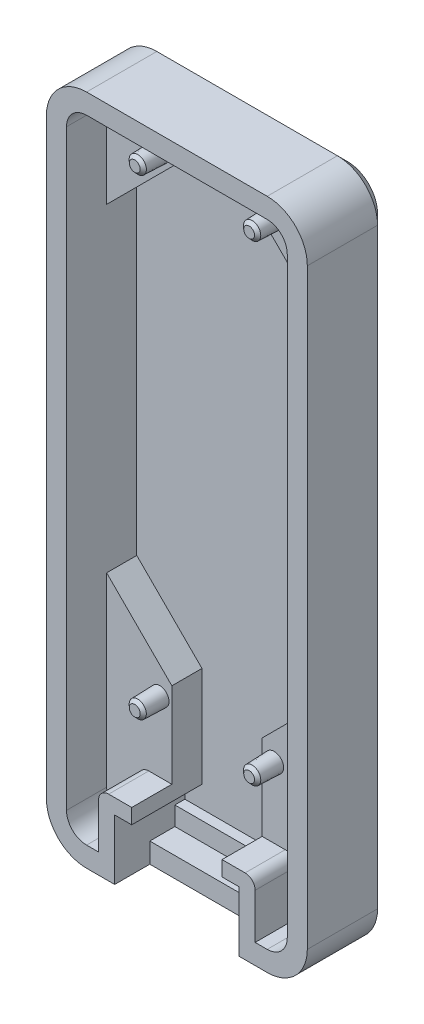
SolidWorks part; units mm, degrees
ref_plane "Front Plane" through (0, 0, 0) normal (0, 0, 1) x (1, 0, 0)
ref_plane "Top Plane" through (0, 0, 0) normal (0, 1, 0) x (1, 0, 0)
ref_plane "Right Plane" through (0, 0, 0) normal (1, 0, 0) x (0, 0, -1)
sketch "Sketch1" plane through (0, 0, 0) normal (0, 0, 1) x (1, 0, 0)
  line L3 (144, 143.2595) -> (140, 143.2595) construction
  line L4 (162, 78.2595) -> (160.8, 78.2595)
  line L5 (140, 139.2595) -> (140, 143.2595) construction
  line L6 (162, 76.2595) -> (166, 76.2595) construction
  line L7 (166, 80.2595) -> (166, 76.2595) construction
  line L8 (162, 76.2595) -> (144, 76.2595)
  line L9 (166, 80.2595) -> (166, 139.2595)
  line L10 (162, 143.2595) -> (144, 143.2595)
  line L11 (140, 80.2595) -> (140, 139.2595)
  line L12 (142, 80.2595) -> (142, 139.2595)
  line L13 (162, 141.2595) -> (144, 141.2595)
  line L14 (164, 80.2595) -> (164, 139.2595)
  line L15 (146.8, 82.2595) -> (146.8, 78.2595)
  line L16 (146.8, 82.2595) -> (148.5, 82.2595)
  line L17 (148.5, 82.2595) -> (148.5, 83.7595)
  line L18 (148.5, 83.7595) -> (146.2, 83.7595)
  line L19 (145.2, 82.7595) -> (145.2, 78.2595)
  line L20 (145.2, 78.2595) -> (144, 78.2595)
  line L21 (162, 78.2595) -> (144, 78.2595) construction
  line L22 (148.5, 82.2595) -> (157.5, 82.2595) construction
  line L23 (153, 82.2595) -> (153, 85.5551) construction
  line L24 (157.5, 82.2595) -> (157.5, 83.7595)
  line L25 (157.5, 83.7595) -> (159.8, 83.7595)
  line L26 (160.8, 82.7595) -> (160.8, 78.2595)
  line L27 (159.2001, 82.2595) -> (159.2001, 78.2595)
  line L28 (159.2001, 82.2595) -> (157.5, 82.2595)
  line L29 (159.2001, 78.2595) -> (146.8, 78.2595)
  arc A0 (144, 76.2595) -> (140, 80.2595) centre (144, 80.2595) cw
  arc A1 (162, 76.2595) -> (166, 80.2595) centre (162, 80.2595) ccw
  arc A2 (166, 139.2595) -> (162, 143.2595) centre (162, 139.2595) ccw
  arc A3 (144, 143.2595) -> (140, 139.2595) centre (144, 139.2595) ccw
  arc A4 (144, 78.2595) -> (142, 80.2595) centre (144, 80.2595) cw
  arc A5 (144, 141.2595) -> (142, 139.2595) centre (144, 139.2595) ccw
  arc A6 (164, 139.2595) -> (162, 141.2595) centre (162, 139.2595) ccw
  arc A7 (162, 78.2595) -> (164, 80.2595) centre (162, 80.2595) ccw
  arc A8 (145.2, 82.7595) -> (146.2, 83.7595) centre (146.2, 82.7595) cw
  arc A9 (160.8, 82.7595) -> (159.8, 83.7595) centre (159.8, 82.7595) ccw
  point P2 (0, 0)
  point P3 (0, 0)
  point P7 (0, 0)
  point P62 (0, 0)
  point P63 (0, 0)
  point P64 (0, 0)
  point P65 (0, 0)
  point P66 (0, 0)
  point P67 (0, 0)
  point P68 (0, 0)
  dimension "D1" = 4
  dimension "D2" = 2
extrude "Boss-Extrude1" add sketch "Sketch1" along normal blind 8
sketch "Sketch2" plane through (0, 0, 0) normal (0, 0, -1) x (-1, 0, 0)
  line L4 (-140, 80.2595) -> (-140, 139.2595)
  line L5 (-144, 143.2595) -> (-162, 143.2595)
  line L6 (-166, 139.2595) -> (-166, 80.2595)
  line L7 (-162, 76.2595) -> (-144, 76.2595)
  line L8 (-140, 80.2595) -> (-140, 139.2595)
  line L9 (-144, 143.2595) -> (-162, 143.2595)
  line L10 (-166, 139.2595) -> (-166, 80.2595)
  line L11 (-162, 76.2595) -> (-144, 76.2595)
  arc A4 (-144, 76.2595) -> (-140, 80.2595) centre (-144, 80.2595) ccw
  arc A5 (-140, 139.2595) -> (-144, 143.2595) centre (-144, 139.2595) ccw
  arc A6 (-162, 143.2595) -> (-166, 139.2595) centre (-162, 139.2595) ccw
  arc A7 (-166, 80.2595) -> (-162, 76.2595) centre (-162, 80.2595) ccw
  arc A8 (-144, 76.2595) -> (-140, 80.2595) centre (-144, 80.2595) ccw
  arc A9 (-140, 139.2595) -> (-144, 143.2595) centre (-144, 139.2595) ccw
  arc A10 (-162, 143.2595) -> (-166, 139.2595) centre (-162, 139.2595) ccw
  arc A11 (-166, 80.2595) -> (-162, 76.2595) centre (-162, 80.2595) ccw
  dimension "D1" = 0
extrude "Boss-Extrude2" add sketch "Sketch2" against normal blind 1
sketch "Sketch3" plane through (0, 0, 1) normal (0, 0, 1) x (1, 0, 0)
  line L0 (142, 130.5618) -> (151.3452, 139.9069)
  line L1 (151.3452, 139.9069) -> (154.6549, 139.9069)
  line L2 (154.6549, 139.9069) -> (164, 130.5617)
  line L3 (142, 98.7595) -> (148.5, 92.2595)
  line L4 (164, 80.2595) -> (164, 139.2595)
  line L5 (162, 141.2595) -> (144, 141.2595)
  line L6 (142, 139.2595) -> (142, 80.2595)
  line L7 (160.8, 78.2595) -> (162, 78.2595)
  line L8 (164, 80.2595) -> (164, 98.7595)
  line L9 (162, 141.2595) -> (144, 141.2595)
  line L10 (142, 139.2595) -> (142, 130.5618)
  line L11 (160.8, 78.2595) -> (162, 78.2595)
  line L12 (148.5, 92.2595) -> (148.5, 83.7595)
  line L18 (157.5, 83.7595) -> (157.5, 92.2595)
  line L19 (157.5, 92.2595) -> (164, 98.7595)
  line L20 (142, 98.7595) -> (142, 80.2595)
  line L21 (164, 130.5617) -> (164, 139.2595)
  line L22 (145.2, 78.2595) -> (145.2, 82.7595)
  line L23 (146.2, 83.7595) -> (148.5, 83.7595)
  line L24 (160.8, 78.2595) -> (160.8, 82.7595)
  line L25 (159.8, 83.7595) -> (157.5, 83.7595)
  line L26 (159.2001, 82.2595) -> (159.2001, 78.2595) construction
  line L27 (146.8, 78.2595) -> (159.2001, 78.2595)
  line L28 (146.8, 78.2595) -> (146.8, 80.1217)
  line L29 (146.8, 80.1217) -> (159.2001, 80.1217)
  line L30 (159.2001, 78.2595) -> (159.2001, 80.1217)
  line L38 (144, 78.2595) -> (145.2, 78.2595)
  line L39 (144, 78.2595) -> (145.2, 78.2595)
  line L40 (145.2, 78.2595) -> (145.2, 82.7595)
  line L42 (146.2, 83.7595) -> (148.5, 83.7595)
  line L44 (148.5, 83.7595) -> (148.5, 82.2595)
  line L46 (148.5, 82.2595) -> (146.8, 82.2595)
  line L48 (146.8, 82.2595) -> (146.8, 78.2595)
  line L50 (146.8, 78.2595) -> (159.2001, 78.2595)
  line L52 (159.2001, 78.2595) -> (159.2001, 82.2595)
  line L54 (159.2001, 82.2595) -> (157.5, 82.2595)
  line L56 (157.5, 82.2595) -> (157.5, 83.7595)
  line L58 (157.5, 83.7595) -> (159.8, 83.7595)
  line L60 (160.8, 82.7595) -> (160.8, 78.2595)
  arc A0 (145.2, 82.7595) -> (146.2, 83.7595) centre (146.2, 82.7595) cw
  arc A4 (162, 78.2595) -> (164, 80.2595) centre (162, 80.2595) ccw
  arc A5 (164, 139.2595) -> (162, 141.2595) centre (162, 139.2595) ccw
  arc A6 (144, 141.2595) -> (142, 139.2595) centre (144, 139.2595) ccw
  arc A7 (142, 80.2595) -> (144, 78.2595) centre (144, 80.2595) ccw
  arc A8 (162, 78.2595) -> (164, 80.2595) centre (162, 80.2595) ccw
  arc A9 (164, 139.2595) -> (162, 141.2595) centre (162, 139.2595) ccw
  arc A10 (144, 141.2595) -> (142, 139.2595) centre (144, 139.2595) ccw
  arc A11 (142, 80.2595) -> (144, 78.2595) centre (144, 80.2595) ccw
  arc A14 (146.2, 83.7595) -> (145.2, 82.7595) centre (146.2, 82.7595) ccw
  arc A16 (160.8, 82.7595) -> (159.8, 83.7595) centre (159.8, 82.7595) ccw
  arc A17 (160.8, 82.7595) -> (159.8, 83.7595) centre (159.8, 82.7595) ccw
  point P31 (0, 0)
  point P32 (0, 0)
  point P33 (0, 0)
  point P34 (0, 0)
  dimension "D1" = 0
extrude "Boss-Extrude3" add sketch "Sketch3" along normal blind 1
sketch "Sketch5" plane through (0, 0, 2) normal (0, 0, 1) x (1, 0, 0)
  circle A0 centre (158.7, 137.7595) radius 1.0048
  circle A1 centre (147.3, 137.7595) radius 1.0048
  circle A2 centre (147.3, 90.7595) radius 1.0048
  circle A3 centre (158.7, 90.7595) radius 1.0048
ref_plane "Plane1" through (0, 0, 6.5) normal (0, 0, 1) x (1, 0, 0)
sketch "Sketch6" plane through (0, 0, 6.5) normal (0, 0, 1) x (1, 0, 0)
  circle A0 centre (147.3, 137.7595) radius 1.0048 construction
  circle A1 centre (158.7, 137.7595) radius 1.0048 construction
  circle A2 centre (147.3, 90.7595) radius 1.0048 construction
  circle A3 centre (158.7, 90.7595) radius 1.0048 construction
  circle A4 centre (147.3, 137.7595) radius 1.0048 construction
  circle A5 centre (158.7, 137.7595) radius 1.0048 construction
  circle A6 centre (147.3, 90.7595) radius 1.0048 construction
  circle A7 centre (158.7, 90.7595) radius 1.0048 construction
  circle A8 centre (147.3, 137.7595) radius 0.85
  circle A9 centre (158.7, 137.7595) radius 0.85
  circle A10 centre (158.7, 90.7595) radius 0.85
  circle A11 centre (147.3, 90.7595) radius 0.85
loft "Loft2" add section "Sketch6" section "Sketch5" start constraint default connector at (159.2756, 90.134, 6.5) connector at (159.4056, 90.0441, 2)
loft "Loft3" add section "Sketch5<3>" section "Sketch6<3>" connector at (147.4441, 89.7651, 2) connector at (147.7636, 90.047, 6.5)
sketch "Sketch5<3>" plane through (0, 0, 2) normal (0, 0, 1) x (1, 0, 0) same geometry as "Sketch5"
sketch "Sketch6<3>" plane through (0, 0, 6.5) normal (0, 0, 1) x (1, 0, 0) same geometry as "Sketch6"
loft "Loft4" add section "Sketch5<4>" section "Sketch6<4>" connector at (158.8197, 136.7618, 2) connector at (158.8332, 136.92, 6.5)
sketch "Sketch5<4>" plane through (0, 0, 2) normal (0, 0, 1) x (1, 0, 0) same geometry as "Sketch5"
sketch "Sketch6<4>" plane through (0, 0, 6.5) normal (0, 0, 1) x (1, 0, 0) same geometry as "Sketch6"
loft "Loft5" add section "Sketch6<6>" section "Sketch5<6>" connector at (147.5382, 136.9435, 6.5) connector at (147.5694, 136.7915, 2)
sketch "Sketch6<6>" plane through (0, 0, 6.5) normal (0, 0, 1) x (1, 0, 0) same geometry as "Sketch6"
sketch "Sketch5<6>" plane through (0, 0, 2) normal (0, 0, 1) x (1, 0, 0) same geometry as "Sketch5"
chamfer "Chamfer1" distance 0.3 angle 45 4 edges at (148.15, 90.7595, 6.5) (159.55, 90.7595, 6.5) (159.55, 137.7595, 6.5) (148.15, 137.7595, 6.5)
chamfer "Chamfer2" distance 1 angle 45 8 edges at (140, 109.7595, 0) (141.1716, 77.431, 0) (141.1716, 142.0879, 0) (153, 76.2595, 0) (153, 143.2595, 0) (164.8285, 77.431, 0) (164.8285, 142.0879, 0) (166, 109.7595, 0)
sketch "Sketch7" plane through (0, 76.2595, 0) normal (0, -1, 0) x (1, 0, 0)
  line L0 (146.8, 8) -> (146.8, 4.5)
  line L3 (146.8, 8) -> (159.2001, 8)
  line L5 (146.8, 4.5) -> (159.2001, 4.5)
  line L6 (159.2001, 4.5) -> (159.2001, 8)
extrude "Cut-Extrude1" cut sketch "Sketch7" against normal blind 3
sketch "Sketch8" plane through (0, 0, 2) normal (0, 0, 1) x (1, 0, 0)
  line L6 (162, 141.2595) -> (144, 141.2595)
  line L7 (142, 139.2595) -> (142, 130.5618)
  line L8 (142, 130.5618) -> (151.3452, 139.9069)
  line L9 (151.3452, 139.9069) -> (154.6549, 139.9069)
  line L10 (154.6549, 139.9069) -> (164, 130.5617)
  line L11 (164, 130.5617) -> (164, 139.2595)
  line L12 (162, 141.2595) -> (144, 141.2595)
  line L13 (142, 139.2595) -> (142, 130.5618)
  line L14 (142, 130.5618) -> (151.3452, 139.9069)
  line L15 (151.3452, 139.9069) -> (154.6549, 139.9069)
  line L16 (154.6549, 139.9069) -> (164, 130.5617)
  line L17 (164, 130.5617) -> (164, 139.2595)
  line L18 (164, 80.2595) -> (164, 98.7595)
  line L19 (164, 98.7595) -> (157.5, 92.2595)
  line L20 (157.5, 92.2595) -> (157.5, 83.7595)
  line L21 (157.5, 83.7595) -> (159.8, 83.7595)
  line L22 (160.8, 82.7595) -> (160.8, 78.2595)
  line L23 (160.8, 78.2595) -> (162, 78.2595)
  line L24 (164, 80.2595) -> (164, 98.7595)
  line L25 (164, 98.7595) -> (157.5, 92.2595)
  line L26 (157.5, 92.2595) -> (157.5, 83.7595)
  line L27 (157.5, 83.7595) -> (159.8, 83.7595)
  line L28 (160.8, 82.7595) -> (160.8, 78.2595)
  line L29 (160.8, 78.2595) -> (162, 78.2595)
  line L30 (146.2, 83.7595) -> (148.5, 83.7595)
  line L31 (148.5, 83.7595) -> (148.5, 92.2595)
  line L32 (148.5, 92.2595) -> (142, 98.7595)
  line L33 (142, 98.7595) -> (142, 80.2595)
  line L34 (144, 78.2595) -> (145.2, 78.2595)
  line L35 (145.2, 78.2595) -> (145.2, 82.7595)
  line L36 (146.2, 83.7595) -> (148.5, 83.7595)
  line L37 (148.5, 83.7595) -> (148.5, 92.2595)
  line L38 (148.5, 92.2595) -> (142, 98.7595)
  line L39 (142, 98.7595) -> (142, 80.2595)
  line L40 (144, 78.2595) -> (145.2, 78.2595)
  line L41 (145.2, 78.2595) -> (145.2, 82.7595)
  arc A2 (164, 139.2595) -> (162, 141.2595) centre (162, 139.2595) ccw
  arc A3 (144, 141.2595) -> (142, 139.2595) centre (144, 139.2595) ccw
  arc A4 (164, 139.2595) -> (162, 141.2595) centre (162, 139.2595) ccw
  arc A5 (144, 141.2595) -> (142, 139.2595) centre (144, 139.2595) ccw
  arc A6 (162, 78.2595) -> (164, 80.2595) centre (162, 80.2595) ccw
  arc A7 (160.8, 82.7595) -> (159.8, 83.7595) centre (159.8, 82.7595) ccw
  arc A8 (162, 78.2595) -> (164, 80.2595) centre (162, 80.2595) ccw
  arc A9 (160.8, 82.7595) -> (159.8, 83.7595) centre (159.8, 82.7595) ccw
  arc A10 (146.2, 83.7595) -> (145.2, 82.7595) centre (146.2, 82.7595) ccw
  arc A11 (142, 80.2595) -> (144, 78.2595) centre (144, 80.2595) ccw
  arc A12 (146.2, 83.7595) -> (145.2, 82.7595) centre (146.2, 82.7595) ccw
  arc A13 (142, 80.2595) -> (144, 78.2595) centre (144, 80.2595) ccw
  dimension "D1" = 0
  dimension "D2" = 0
  dimension "D3" = 0
extrude "Boss-Extrude4" add sketch "Sketch8" along normal blind 2
